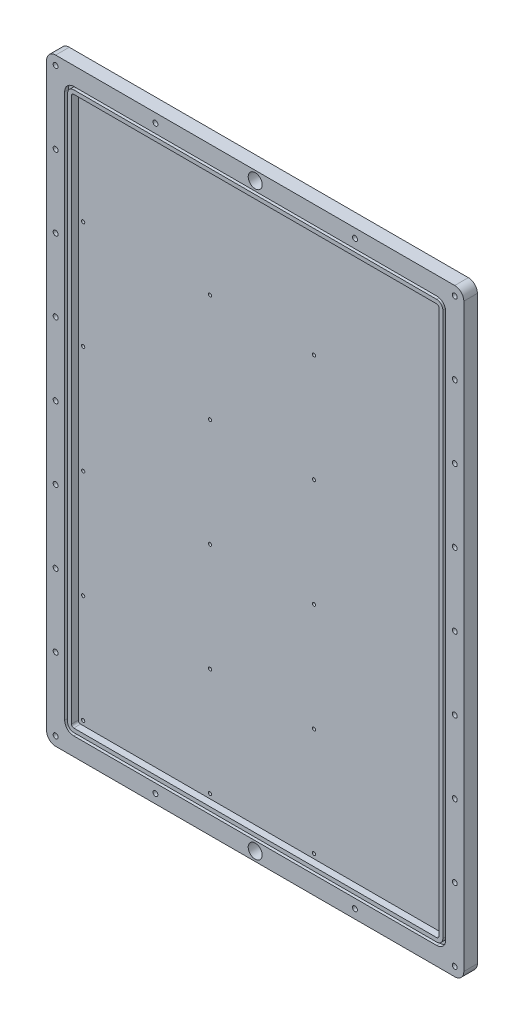
SolidWorks part; units mm, degrees
ref_plane "Front Plane" through (0, 0, 0) normal (0, 0, 1) x (1, 0, 0)
ref_plane "Top Plane" through (0, 0, 0) normal (0, 1, 0) x (1, 0, 0)
ref_plane "Right Plane" through (0, 0, 0) normal (1, 0, 0) x (0, 0, -1)
sketch "Sketch1" plane through (0, 0, 0) normal (0, 0, 1) x (1, 0, 0)
  line L1 (0, 0) -> (292.0492, 0)
  line L2 (0, 0) -> (0, 419.0492)
  line L3 (0, 419.0492) -> (292.0492, 419.0492)
  line L4 (292.0492, 0) -> (292.0492, 419.0492)
  dimension "D1" = 419.0492
  dimension "D2" = 292.0492
extrude "Boss-Extrude1" add sketch "Sketch1" along normal blind 9.525
sketch "Sketch4" plane through (0, 0, 9.525) normal (0, 0, 1) x (1, 0, 0)
  line L0 (91.477, 6.3246) -> (91.477, 0) construction
  line L1 (0, 0) -> (292.0492, 0) construction
  line L2 (6.3246, 94.9672) -> (0, 94.9672) construction
  line L4 (6.3246, 412.7246) -> (285.7246, 412.7246) construction
  line L5 (6.3246, 412.7246) -> (6.3246, 6.3246) construction
  line L6 (6.3246, 6.3246) -> (285.7246, 6.3246) construction
  line L7 (285.7246, 412.7246) -> (285.7246, 6.3246) construction
  line L11 (0, 419.0492) -> (0, 0) construction
  line L12 (285.7246, 110.613) -> (292.0492, 110.613) construction
  line L13 (292.0492, 0) -> (292.0492, 419.0492) construction
  line L14 (125.5626, 412.7246) -> (125.5626, 419.0492) construction
  line L15 (292.0492, 419.0492) -> (0, 419.0492) construction
  circle A0 centre (6.3246, 6.3246) radius 1.7272
  circle A1 centre (6.3246, 412.7246) radius 1.7272
  circle A2 centre (285.7246, 412.7246) radius 1.7272
  circle A3 centre (285.7246, 6.3246) radius 1.7272
  dimension "D5" = 3.4544
  dimension "D1" = 279.4
  dimension "D2" = 406.4
extrude "Cut-Extrude1" cut sketch "Sketch4" against normal through all
sketch "Sketch5" plane through (0, 0, 9.525) normal (0, 0, 1) x (1, 0, 0)
  line L0 (0, 209.5246) -> (12.6746, 209.5246) construction
  line L1 (19.0246, 406.3746) -> (273.0246, 406.3746)
  line L2 (12.6746, 400.0246) -> (12.6746, 19.0246)
  line L3 (19.0246, 12.6746) -> (273.0246, 12.6746)
  line L4 (279.3746, 400.0246) -> (279.3746, 19.0246)
  line L5 (0, 419.0492) -> (0, 0) construction
  line L6 (279.3746, 209.5246) -> (292.0492, 209.5246) construction
  line L8 (19.0246, 14.7066) -> (273.0246, 14.7066)
  line L9 (14.7066, 400.0246) -> (14.7066, 19.0246)
  line L10 (19.0246, 404.3426) -> (273.0246, 404.3426)
  line L11 (277.3426, 400.0246) -> (277.3426, 19.0246)
  line L12 (292.0492, 0) -> (292.0492, 419.0492) construction
  line L13 (146.0246, 12.6746) -> (146.0246, 0) construction
  line L14 (0, 0) -> (292.0492, 0) construction
  line L15 (146.0246, 406.3746) -> (146.0246, 419.0492) construction
  line L16 (292.0492, 419.0492) -> (0, 419.0492) construction
  arc A0 (273.0246, 12.6746) -> (279.3746, 19.0246) centre (273.0246, 19.0246) ccw
  arc A1 (12.6746, 19.0246) -> (19.0246, 12.6746) centre (19.0246, 19.0246) ccw
  arc A2 (273.0246, 406.3746) -> (279.3746, 400.0246) centre (273.0246, 400.0246) cw
  arc A3 (19.0246, 406.3746) -> (12.6746, 400.0246) centre (19.0246, 400.0246) ccw
  arc A4 (14.7066, 19.0246) -> (19.0246, 14.7066) centre (19.0246, 19.0246) ccw
  arc A5 (19.0246, 404.3426) -> (14.7066, 400.0246) centre (19.0246, 400.0246) ccw
  arc A6 (273.0246, 404.3426) -> (277.3426, 400.0246) centre (273.0246, 400.0246) cw
  arc A7 (273.0246, 14.7066) -> (277.3426, 19.0246) centre (273.0246, 19.0246) ccw
  dimension "D5" = 6.35
  dimension "D1" = 266.7
  dimension "D2" = 393.7
  dimension "D6" = 2.032
  dimension "D7" = 2.032
extrude "Cut-Extrude2" cut sketch "Sketch5" against normal blind 2.54 contours L1 A3 L2 A1 L3 A0 L4 A2 A7 L8 A4 L9 A5 L10 A6 L11 region at (146.0246, 405.8991, 9.525)
pattern_linear "LPattern3" count 4 spacing 69.85 along (1, 0, 0) of face at (8.0518, 412.7246, 0) of face at (8.0518, 6.3246, 0)
pattern_linear "LPattern4" count 8 spacing 50.8 along (0, -1, 0) of face at (8.0518, 412.7246, 0) of face at (287.4518, 412.7246, 0)
sketch "Sketch6" plane through (0, 0, 9.525) normal (0, 0, 1) x (1, 0, 0)
  line L4 (274.6121, 19.0246) -> (274.6121, 400.0246)
  line L5 (274.6121, 19.0246) -> (274.6121, 400.0246)
  line L6 (273.0246, 401.6121) -> (19.0246, 401.6121)
  line L7 (273.0246, 401.6121) -> (19.0246, 401.6121)
  line L8 (17.4371, 400.0246) -> (17.4371, 19.0246)
  line L9 (17.4371, 400.0246) -> (17.4371, 19.0246)
  line L10 (19.0246, 17.4371) -> (273.0246, 17.4371)
  line L11 (19.0246, 17.4371) -> (273.0246, 17.4371)
  arc A4 (273.0246, 17.4371) -> (274.6121, 19.0246) centre (273.0246, 19.0246) ccw
  arc A5 (273.0246, 17.4371) -> (274.6121, 19.0246) centre (273.0246, 19.0246) ccw
  arc A6 (274.6121, 400.0246) -> (273.0246, 401.6121) centre (273.0246, 400.0246) ccw
  arc A7 (274.6121, 400.0246) -> (273.0246, 401.6121) centre (273.0246, 400.0246) ccw
  arc A8 (19.0246, 401.6121) -> (17.4371, 400.0246) centre (19.0246, 400.0246) ccw
  arc A9 (19.0246, 401.6121) -> (17.4371, 400.0246) centre (19.0246, 400.0246) ccw
  arc A10 (17.4371, 19.0246) -> (19.0246, 17.4371) centre (19.0246, 19.0246) ccw
  arc A11 (17.4371, 19.0246) -> (19.0246, 17.4371) centre (19.0246, 19.0246) ccw
  dimension "D1" = 2.7305
extrude "Cut-Extrude3" cut sketch "Sketch6" against normal blind 4.7625
sketch "Sketch7" plane through (0, 0, 4.7625) normal (0, 0, 1) x (1, 0, 0)
  line L0 (273.0246, 401.6121) -> (19.0246, 401.6121) construction
  line L1 (20.8407, 398.4371) -> (271.2085, 398.4371) construction
  line L2 (20.8407, 398.4371) -> (20.8407, 20.6121) construction
  line L3 (20.8407, 20.6121) -> (271.2085, 20.6121) construction
  line L4 (271.2085, 398.4371) -> (271.2085, 20.6121) construction
  line L5 (17.4371, 400.0246) -> (17.4371, 19.0246) construction
  line L6 (274.6121, 19.0246) -> (274.6121, 400.0246) construction
  line L7 (19.0246, 17.4371) -> (273.0246, 17.4371) construction
  line L8 (17.4371, 400.0246) -> (17.4371, 19.0246) construction
  line L9 (274.6121, 19.0246) -> (274.6121, 400.0246) construction
  circle A0 centre (20.8407, 398.4371) radius 1.1303
  circle A1 centre (271.2085, 398.4371) radius 1.1303
  circle A2 centre (20.8407, 20.6121) radius 1.1303
  circle A3 centre (109.6391, 20.6121) radius 1.1303
  circle A4 centre (109.6391, 398.4371) radius 1.1303
  circle A5 centre (182.4101, 398.4371) radius 1.1303
  circle A6 centre (182.4101, 20.6121) radius 1.1303
  circle A7 centre (271.2085, 20.6121) radius 1.1303
  dimension "D5" = 2.2606
  dimension "D1" = 3.175
  dimension "D2" = 3.4036
  dimension "D3" = 3.4036
  dimension "D4" = 3.175
  dimension "D6" = 92.202
  dimension "D7" = 92.202
  dimension "D8" = 88.7984
  dimension "D9" = 88.7984
extrude "Cut-Extrude4" cut sketch "Sketch7" against normal blind 3.175
sketch "Sketch8" plane through (0, 0, 9.525) normal (0, 0, 1) x (1, 0, 0)
  circle A0 centre (146.0246, 412.7246) radius 4.9022
  circle A1 centre (146.0246, 6.3246) radius 4.9022
  dimension "D1" = 9.8044
extrude "Cut-Extrude5" cut sketch "Sketch8" against normal through all
fillet "Fillet1" radius 6.35 4 edges at (292.0492, 0, 4.7625) (0, 0, 4.7625) (292.0492, 419.0492, 4.7625) (0, 419.0492, 4.7625)
pattern_linear "LPattern10" count 5 spacing 75.565 along (0, -1, 0) of "Cut-Extrude4"
